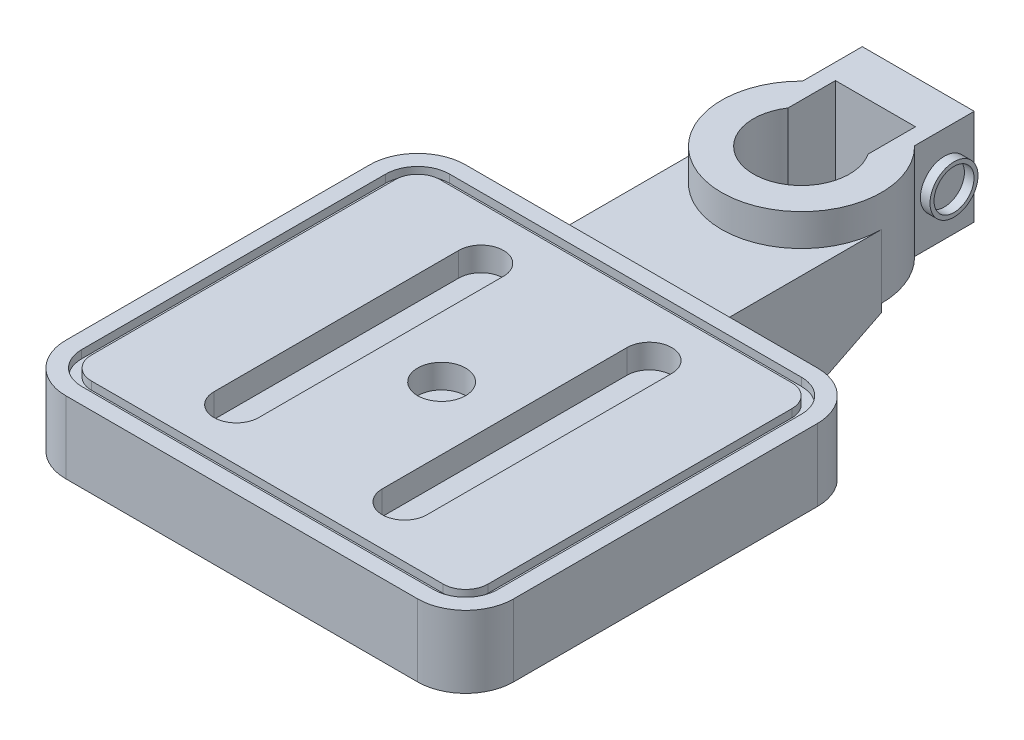
SolidWorks part; units mm, degrees
ref_plane "Front Plane" through (0, 0, 0) normal (0, 0, 1) x (1, 0, 0)
ref_plane "Top Plane" through (0, 0, 0) normal (0, 1, 0) x (1, 0, 0)
ref_plane "Right Plane" through (0, 0, 0) normal (1, 0, 0) x (0, 0, -1)
sketch "Sketch1" plane through (0, 0, 0) normal (0, 1, 0) x (1, 0, 0)
  line L5 (-35, 73) -> (35, 73)
  line L6 (-35, 73) -> (-35, 35.7071)
  line L8 (35, 73) -> (35, 35.7071)
  arc A0 (-35, 35.7071) -> (35, 35.7071) centre (0, 0) ccw
  point P3 (0, 50)
  point P4 (0, 50)
  dimension "D1" = 100
  dimension "D2" = 70
extrude "Boss-Extrude1" add sketch "Sketch1" along normal blind 40
sketch "Sketch2" plane through (0, 40, 0) normal (0, 1, 0) x (1, 0, 0)
  line L2 (-25.015, 16.5876) -> (-25.015, 46.245)
  line L3 (-25.015, 46.245) -> (25.015, 46.245)
  line L4 (25.015, 16.5876) -> (25.015, 46.245)
  arc A0 (-25.015, 16.5876) -> (25.015, 16.5876) centre (0, 0) ccw
  point P3 (0, 30.015)
  dimension "D1" = 60.03
  dimension "D3" = 50.03
extrude "Cut-Extrude1" cut sketch "Sketch2" against normal blind 66
sketch "Sketch3" plane through (0, 0, 0) normal (0, 1, 0) x (1, 0, 0)
  line L0 (30.015, 0) -> (50, 0)
  line L1 (-50, -100) -> (50, -100)
  line L2 (-50, -100) -> (-50, 0)
  line L3 (-50, 0) -> (-30.015, 0)
  line L4 (50, -100) -> (50, 0)
  line L5 (-50, -100) -> (50, 0) construction
  line L6 (-50, 0) -> (50, -100) construction
  arc A0 (-35, 35.7071) -> (35, 35.7071) centre (0, 0) ccw construction
  arc A1 (-30.015, 0) -> (30.015, 0) centre (0, 0) ccw
  point P0 (0, -50)
  dimension "D1" = 100
extrude "Boss-Extrude2" add sketch "Sketch3" along normal up to surface and the other way blind 55 up to face at (0, 40, -19.7657)
sketch "Sketch4" plane through (50, 0, 0) normal (1, 0, 0) x (0, 0, -1)
  line L0 (-100, -55) -> (0, -5.0276)
  line L1 (0, -55) -> (0, 0) construction
  line L2 (0, -5.0276) -> (0, -55)
  line L3 (0, -55) -> (-100, -55)
extrude "Cut-Extrude2" cut sketch "Sketch4" against normal blind 256
sketch "Sketch5" plane through (0, 40, 0) normal (0, 1, 0) x (1, 0, 0)
  line L0 (-50, -100) -> (50, -100) construction
  line L1 (-110, -350) -> (110, -350)
  line L2 (-140, -320) -> (-140, -130)
  line L4 (140, -320) -> (140, -130)
  line L5 (-140, -350) -> (0, -100) construction
  line L6 (0, -100) -> (140, -350) construction
  line L7 (-110, -100) -> (110, -100)
  arc A0 (110, -350) -> (140, -320) centre (110, -320) ccw
  arc A1 (-110, -350) -> (-140, -320) centre (-110, -320) cw
  arc A2 (-110, -100) -> (-140, -130) centre (-110, -130) ccw
  arc A3 (110, -100) -> (140, -130) centre (110, -130) cw
  point P0 (0, -100)
  dimension "D2" = 30
  dimension "D1" = 280
extrude "Boss-Extrude3" add sketch "Sketch5" along normal blind 5 and the other way up to surface other way up to face at (0, 0, -28.9033)
sketch "Sketch6" plane through (0, 40, 0) normal (0, 1, 0) x (1, 0, 0)
  line L2 (-35, 35.7071) -> (-35, 73)
  line L3 (-35, 73) -> (35, 73)
  line L4 (35, 35.7071) -> (35, 73)
  line L6 (-25.015, 16.5876) -> (-25.015, 46.245)
  line L7 (-25.015, 46.245) -> (25.015, 46.245)
  line L8 (25.015, 16.5876) -> (25.015, 46.245)
  arc A0 (-35, 35.7071) -> (35, 35.7071) centre (0, 0) ccw
  arc A1 (-25.015, 16.5876) -> (25.015, 16.5876) centre (0, 0) ccw
  point P3 (0, 50)
  point P7 (0, 30.015)
extrude "Boss-Extrude4" add sketch "Sketch6" along normal blind 20
sketch "Sketch7" plane through (0, 45, 0) normal (0, 1, 0) x (1, 0, 0)
  line L8 (130, -320) -> (130, -130)
  line L9 (110, -110) -> (-110, -110)
  line L10 (-130, -130) -> (-130, -320)
  line L11 (-110, -340) -> (110, -340)
  line L12 (130, -320) -> (130, -130)
  line L13 (110, -110) -> (-110, -110)
  line L14 (-130, -130) -> (-130, -320)
  line L15 (-110, -340) -> (110, -340)
  arc A8 (110, -340) -> (130, -320) centre (110, -320) ccw
  arc A9 (130, -130) -> (110, -110) centre (110, -130) ccw
  arc A10 (-110, -110) -> (-130, -130) centre (-110, -130) ccw
  arc A11 (-130, -320) -> (-110, -340) centre (-110, -320) ccw
  arc A12 (110, -340) -> (130, -320) centre (110, -320) ccw
  arc A13 (130, -130) -> (110, -110) centre (110, -130) ccw
  arc A14 (-110, -110) -> (-130, -130) centre (-110, -130) ccw
  arc A15 (-130, -320) -> (-110, -340) centre (-110, -320) ccw
  dimension "D1" = 10
extrude "Cut-Extrude3" cut sketch "Sketch7" against normal blind 5
sketch "Sketch8" plane through (0, 40, 0) normal (0, 1, 0) x (1, 0, 0)
  line L8 (124, -320) -> (124, -130)
  line L9 (110, -116) -> (-110, -116)
  line L10 (-124, -130) -> (-124, -320)
  line L11 (-110, -334) -> (110, -334)
  line L12 (124, -320) -> (124, -130)
  line L13 (110, -116) -> (-110, -116)
  line L14 (-124, -130) -> (-124, -320)
  line L15 (-110, -334) -> (110, -334)
  arc A8 (110, -334) -> (124, -320) centre (110, -320) ccw
  arc A9 (124, -130) -> (110, -116) centre (110, -130) ccw
  arc A10 (-110, -116) -> (-124, -130) centre (-110, -130) ccw
  arc A11 (-124, -320) -> (-110, -334) centre (-110, -320) ccw
  arc A12 (110, -334) -> (124, -320) centre (110, -320) ccw
  arc A13 (124, -130) -> (110, -116) centre (110, -130) ccw
  arc A14 (-110, -116) -> (-124, -130) centre (-110, -130) ccw
  arc A15 (-124, -320) -> (-110, -334) centre (-110, -320) ccw
  dimension "D1" = 6
extrude "Boss-Extrude5" add sketch "Sketch8" along normal blind 5
sketch "Sketch9" plane through (0, 45, 0) normal (0, 1, 0) x (1, 0, 0)
  line L1 (-51.8235, -301.5186) -> (-51.8235, -148.4814) construction
  line L2 (-65.8235, -301.5186) -> (-65.8235, -148.4814)
  line L3 (-37.8235, -301.5186) -> (-37.8235, -148.4814)
  line L4 (53.3862, -301.5186) -> (53.3862, -148.4814) construction
  line L5 (39.3862, -301.5186) -> (39.3862, -148.4814)
  line L6 (67.3862, -301.5186) -> (67.3862, -148.4814)
  arc A0 (-65.8235, -301.5186) -> (-37.8235, -301.5186) centre (-51.8235, -301.5186) ccw
  arc A1 (-37.8235, -148.4814) -> (-65.8235, -148.4814) centre (-51.8235, -148.4814) ccw
  arc A2 (39.3862, -301.5186) -> (67.3862, -301.5186) centre (53.3862, -301.5186) ccw
  arc A3 (67.3862, -148.4814) -> (39.3862, -148.4814) centre (53.3862, -148.4814) ccw
  circle A4 centre (0, -225) radius 15
  point P3 (46.3862, -225)
  point P5 (-51.8235, -225)
  point P11 (53.3862, -225)
  dimension "D1" = 14
  dimension "D2" = 14
  dimension "D3" = 30
extrude "Cut-Extrude5" cut sketch "Sketch9" against normal blind 15
sketch "Sketch10" plane through (0, 0, 100) normal (0, 0, 1) x (1, 0, 0)
  line L8 (50, -55) -> (50, 0)
  line L9 (50, 0) -> (-50, 0)
  line L10 (-50, 0) -> (-50, -55)
  line L11 (-50, -55) -> (50, -55)
  line L12 (50, -55) -> (50, 0)
  line L13 (50, 0) -> (-50, 0)
  line L14 (-50, 0) -> (-50, -55)
  line L15 (-50, -55) -> (50, -55)
  dimension "D1" = 0
extrude "Boss-Extrude6" add sketch "Sketch10" along normal blind 140
sketch "Sketch11" plane through (0, -55, 0) normal (0, -1, 0) x (1, 0, 0)
  line L1 (-50, 240) -> (50, 240)
  line L2 (-50, 240) -> (-50, 218.9898)
  line L4 (50, 240) -> (50, 218.9898)
  arc A0 (50, 218.9898) -> (-50, 218.9898) centre (0, 170) ccw
  line M2 (50, 100) -> (50, 240)
  line M3 (50, 240) -> (-50, 240)
  line M4 (-50, 240) -> (-50, 100)
extrude "Cut-Extrude6" cut sketch "Sketch11" against normal up to surface (55 mm away) contours A0 M2 M3 | A0 L1 M4 region at (37.9063, -55, 233.9005) region at (-37.9063, -55, 233.9005) up to face at (0, 0, 206.6667)
sketch "Sketch12" plane through (35, 0, 0) normal (1, 0, 0) x (0, 0, -1)
  circle A0 centre (54.3536, 30) radius 15
  dimension "D1" = 30
extrude "Boss-Extrude7" add sketch "Sketch12" along normal blind 6
sketch "Sketch13" plane through (41, 0, 0) normal (1, 0, 0) x (0, 0, -1)
  circle A0 centre (54.3536, 30) radius 12.5
  dimension "D1" = 25
extrude "Cut-Extrude7" cut sketch "Sketch13" against normal blind 6
